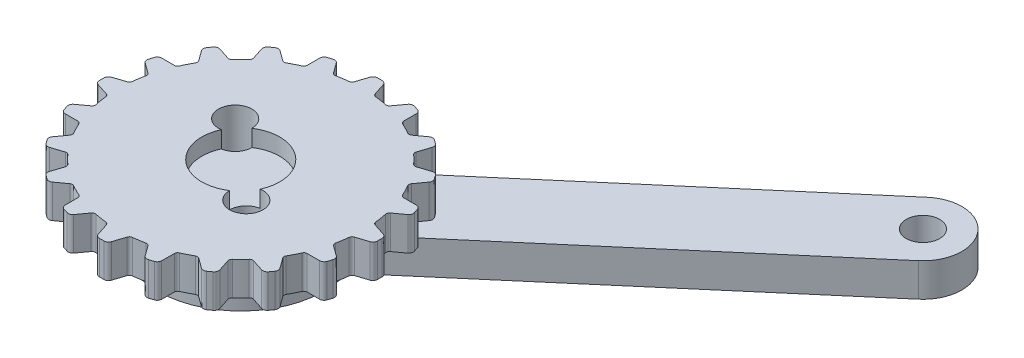
SolidWorks part; units mm, degrees
material "ABS"
ref_plane "Front Plane" through (0, 0, 0) normal (0, 0, 1) x (1, 0, 0)
ref_plane "Top Plane" through (0, 0, 0) normal (0, 1, 0) x (1, 0, 0)
ref_plane "Right Plane" through (0, 0, 0) normal (1, 0, 0) x (0, 0, -1)
sketch "Sketch1" plane through (0, 0, 0) normal (0, 1, 0) x (1, 0, 0)
  line L0 (0, 12.5) -> (0, -12.5) construction
  line L1 (-1, 10.9545) -> (-0.5899, 12.2138)
  line L2 (-0.2096, 12.49) -> (0.2096, 12.49)
  line L3 (0.5899, 12.2138) -> (1, 10.9545)
  circle A0 centre (0, 0) radius 12.5
  circle A1 centre (0, 0) radius 11
  arc A2 (0.2096, 12.49) -> (0.5899, 12.2138) centre (0.2096, 12.09) cw
  arc A3 (-0.5899, 12.2138) -> (-0.2096, 12.49) centre (-0.2096, 12.09) cw
  circle A4 centre (0, 0) radius 3.5
  circle A5 centre (0, 5) radius 1 construction
  circle A6 centre (0, -5) radius 1 construction
  circle A7 centre (0, 0) radius 11.75 construction
  circle A8 centre (0, 0) radius 7.5
  point P12 (0.5, 12.49)
  point P15 (-0.5, 12.49)
  dimension "D1" = 25
  dimension "D2" = 22
  dimension "D3" = 1
  dimension "D6" = 0.4
  dimension "D7" = 7
  dimension "D8" = 2
  dimension "D11" = 2
  dimension "D12" = 23.5
  dimension "D13" = 15
  dimension "D4" = 1
  dimension "D5" = 0.5
  dimension "D9" = 5
  dimension "D10" = 5
extrude "Boss-Extrude1" add sketch "Sketch1" along normal mid plane 3 contours L0 A1 | A1 L0 | A8 A4 A5 A6 region at (0, 0, -10.6889) region at (-7.2879, 0, 0)
extrude "Boss-Extrude2" add sketch "Sketch1<3>" along normal mid plane 3 contours L0 L2 A3 L1 A1 region at (0, 0, -11.6439)
sketch "Sketch1<3>" plane through (0, 0, 0) normal (0, 1, 0) x (1, 0, 0) same geometry as "Sketch1"
fillet "Fillet1" radius 0.3 2 edges at (1, 0, -10.9545) (-1, 0, -10.9545)
pattern_circular "CirPattern1" count 20 over 360 about axis through (0, 1.5, 0) along (0, 1, 0) of "Boss-Extrude2", "Fillet1"
sketch "Sketch2" plane through (0, -1.5, 0) normal (0, -1, 0) x (1, 0, 0)
  line L0 (2.4222, -2.5264) -> (33.064, -28.2379) construction
  line L1 (2.273, 2.6615) -> (35.337, -25.5765)
  line L2 (-2.273, -2.6615) -> (30.791, -30.8994)
  line L3 (2.4222, -2.5264) -> (-22.6289, -2.5264) construction
  circle A0 centre (0, 0) radius 3.5 construction
  arc A2 (30.791, -30.8994) -> (35.337, -25.5765) centre (33.064, -28.2379) ccw
  arc A3 (-2.273, -2.6615) -> (2.273, 2.6615) centre (0, 0) ccw
  dimension "D3" = 3.5
  dimension "D1" = 7
  dimension "D2" = 40
  dimension "D4" = 140
extrude "Boss-Extrude3" add sketch "Sketch2" along normal blind 3 contours A3 L2 A2 L1 region at (18.6223, -1.5, -15.9042)
sketch "Sketch3" plane through (0, -1.5, 0) normal (0, 1, 0) x (1, 0, 0)
  circle A0 centre (33.064, 28.2379) radius 1.5
  dimension "D1" = 3
extrude "Cut-Extrude1" cut sketch "Sketch3" against normal through all
extrude "Boss-Extrude4" add sketch "Sketch1<4>" against normal blind 5 contours A8
sketch "Sketch1<4>" plane through (0, 0, 0) normal (0, 1, 0) x (1, 0, 0) same geometry as "Sketch1"
sketch "Sketch4" plane through (0, -5, 0) normal (0, -1, 0) x (1, 0, 0)
  line L0 (-5.7032, -4.8707) -> (5.7032, 4.8707) construction
  line L1 (-5.7032, -4.8707) -> (5.7032, -4.8707) construction
  arc A0 (7.3171, -1.6464) -> (2.7711, -6.9693) centre (0, 0) ccw construction
  circle A1 centre (0, 0) radius 7.5 construction
  arc A2 (2.7711, -6.9693) -> (7.3171, -1.6464) centre (0, 0) ccw construction
  circle A3 centre (3.4219, 2.9224) radius 1.5
  circle A4 centre (-3.4219, -2.9224) radius 1.5
  dimension "D2" = 3
  dimension "D1" = 15
  dimension "D3" = 3
  dimension "D4" = 4.5
extrude "Cut-Extrude2" cut sketch "Sketch4" against normal through all both
